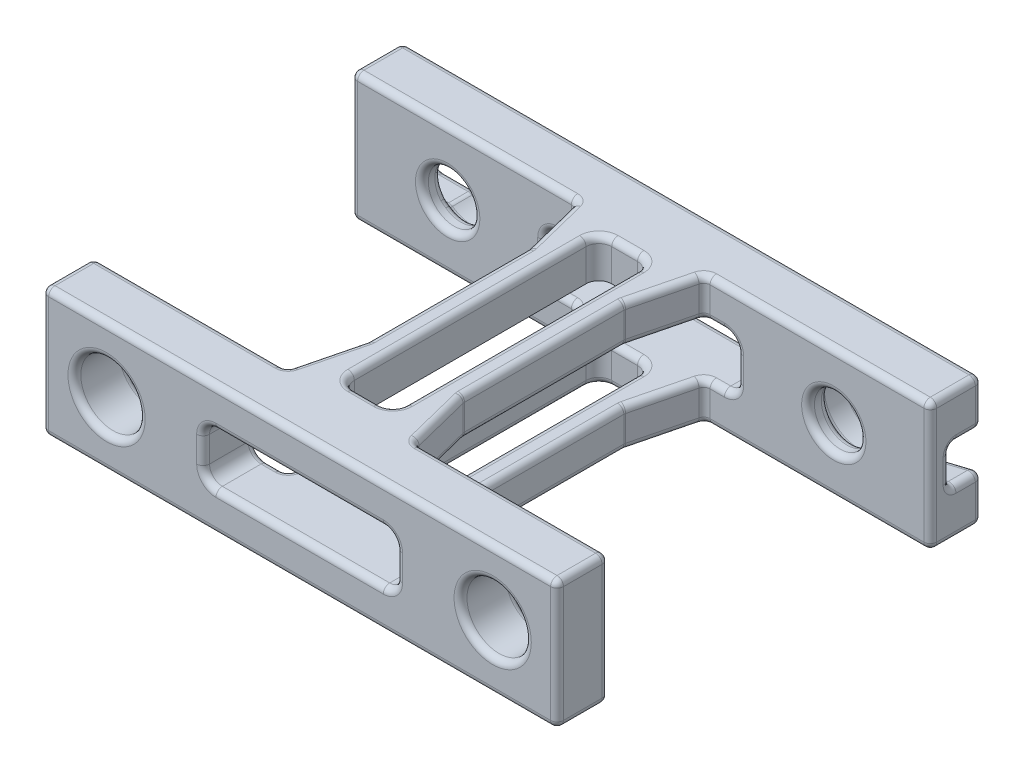
SolidWorks part; units mm, degrees
material "Custom Plastic"
ref_plane "Front Plane" through (0, 0, 0) normal (0, 0, 1) x (1, 0, 0)
ref_plane "Top Plane" through (0, 0, 0) normal (0, 1, 0) x (1, 0, 0)
ref_plane "Right Plane" through (0, 0, 0) normal (1, 0, 0) x (0, 0, -1)
sketch "Sketch1" plane through (0, 0, 0) normal (0, 0, 1) x (1, 0, 0)
  line L1 (-15, 10) -> (15, 10)
  line L2 (-15, 10) -> (-15, -10)
  line L3 (-15, -10) -> (15, -10)
  line L4 (15, 10) -> (15, -10)
  line L5 (-15, 10) -> (15, -10) construction
  line L6 (-15, -10) -> (15, 10) construction
  circle A0 centre (0, 0) radius 2
  dimension "D3" = 4
  dimension "D1" = 20
  dimension "D2" = 30
extrude "Boss-Extrude1" add sketch "Sketch1" along normal blind 8
sketch "Sketch2" plane through (0, 0, 0) normal (0, 0, -1) x (-1, 0, 0)
  line L0 (0, 5.5) -> (0, -5.5) construction
  line L1 (-3.4911, 4.25) -> (-3.4911, -4.25)
  line L2 (-3.4911, 4.25) -> (-8.4911, 4.25)
  line L3 (0, 0) -> (-5.5, 0) construction
  line L4 (-3.4911, -4.25) -> (-8.4911, -4.25)
  line L5 (-18.2077, 1.8863) -> (-8.4911, 4.25)
  line L6 (-18.2077, -1.8863) -> (-8.4911, -4.25)
  circle A1 centre (0, 0) radius 5.5
  arc A2 (0.5609, 0) -> (-17.543, 0) centre (-8.4911, 4.25) ccw
  arc A3 (0.5609, 0) -> (-17.543, 0) centre (-8.4911, -4.25) cw
  arc A4 (-18.2077, 1.8863) -> (-18.2077, -1.8863) centre (-17.543, 0) ccw
  line M3 (-15, 10) -> (-15, -10)
  circle M7 centre (0, 0) radius 2
  dimension "D1" = 11
  dimension "D4" = 20
  dimension "D5" = 4
  dimension "D2" = 8.5
  dimension "D3" = 5
extrude "Cut-Extrude1" cut sketch "Sketch2" against normal blind 5 contours A3 A1 A2 M7 | A3 A2 A1 L1 M7 | L1 A1 | A1 L2 L5 L6 L4 M3
sketch "Sketch3" plane through (0, 10, 0) normal (0, 1, 0) x (1, 0, 0)
  line L0 (-22.5, -53) -> (-22.5, -8)
  line L1 (15, -8) -> (-15, -8)
  line L2 (15, -8) -> (15, 0)
  line L3 (15, 0) -> (-15, 0)
  line L4 (-15, -8) -> (-15, 0)
  line L5 (-15, -8) -> (-30, -8)
  line L6 (-15, -8) -> (-15, 0)
  line L7 (-15, 0) -> (-30, 0)
  line L8 (-30, -8) -> (-30, 0)
  line L9 (-30, -8) -> (-15, -8)
  line L10 (-30, -8) -> (-30, -53)
  line L11 (-30, -53) -> (-15, -53)
  line L12 (-15, -8) -> (-15, -53)
  line L13 (-30, -53) -> (10, -53)
  line L14 (-30, -53) -> (-30, -61)
  line L15 (-30, -61) -> (10, -61)
  line L16 (10, -53) -> (10, -61)
  line L17 (-22.5, -30.5) -> (-15, -30.5) construction
  line L18 (-15, -53) -> (-22.5, -43)
  line L19 (-15, -8) -> (-22.5, -18)
  line L20 (-22.5, -18) -> (-20, -8)
  line L21 (-22.5, -43) -> (-20, -53)
  line M18 (-15, 0) -> (-15, -8)
  dimension "D1" = 15
  dimension "D2" = 45
  dimension "D3" = 8
  dimension "D4" = 40
  dimension "D5" = 10
  dimension "D6" = 5
extrude "Boss-Extrude2" add sketch "Sketch3" against normal blind 20 separate body contours L16 L13 L11 L14 L15 | L12 L5 L10 L11 | L8 L5 L7 M18 | L0 L20 L9 | L21 L0 L11
sketch "Sketch4" plane through (0, 0, 53) normal (0, 0, -1) x (-1, 0, 0)
  circle A0 centre (0, 0) radius 5
  dimension "10" = 10
extrude "Cut-Extrude2" cut sketch "Sketch4" along normal blind 20 and the other way through all
sketch "Sketch5" plane through (0, 0, 5) normal (0, 0, -1) x (-1, 0, 0)
  circle A0 centre (0, 0) radius 2
  circle A1 centre (0, 0) radius 4
  dimension "D1" = 8
extrude "Cut-Extrude3" cut sketch "Sketch5" against normal through all
mirror "Mirror4" about plane through (-30, -10, 0) normal (-1, 0, 0) of bodies 104 105
combine bodies "Combine1" operation type add bodies to combine 106 104 107 105
fillet "Fillet4" radius 1 85 edges at (-37.5, -10, 30.5) (-55, 10, 53) (-70, 10, 57) (-30, 10, 61) (-30, 10, 0) (-38.75, -10, 13) (-57.5, 10, 8) (-38.75, 10, 13) (-37.5, 10, 30.5) (-38.75, 10, 48) (-57.5, -10, 8) (-40, 0, 53) (-70, 0, 53) (-70, 0, 61) (-40, 0, 8) (-37.5, 0, 18) (-37.5, 0, 43) (-30, -10, 0) (-30, -10, 61) (-38.75, -10, 48) (-70, -10, 57) (-55, -10, 53) (-21.25, 10, 48) (-22.5, 0, 43) (-5, 10, 53) (-20, 0, 53) (10, 10, 57) (10, 0, 53) (10, 0, 61) (11.7455, 3.4583, 0) (5.9911, -4.25, 0) (-2.5, 10, 8) (15, 0, 8) (-21.25, -10, 13) (-20, 0, 8) (-22.5, -10, 30.5) (-22.5, 0, 18) (-21.25, -10, 48) (-5, -10, 53) (10, -10, 57) (-2.5, -10, 8) (-22.5, 10, 30.5) (-21.25, 10, 13) (15, 10, 4) (15, -6.3333, 0) (15, 2.6666, 2.5) (15, 6.3333, 0) (15, -10, 4) (5.9911, -4.25, 5) (8.4911, -4.25, 2.5) (11.7455, -3.4583, 0) (15, -2.6666, 2.5) (11.7455, 3.4583, 5) (8.4911, 4.25, 2.5) (5.9911, 4.25, 0) (3.4911, 4.25, 2.5) (-5.5, 0, 0) (3.4911, -4.25, 2.5) (-5.5, 0, 5) (5.9911, 4.25, 5) (15, 0, 5) (11.7455, -3.4583, 5) (4, 0, 8) (-54.5, 0, 0) (-65.9911, 4.25, 0) (-75, 6.3333, 0) (-75, -6.3333, 0) (-71.7455, -3.4583, 0) (-75, 0, 8) (-75, 10, 4) (-75, 0, 5) (-75, -2.6666, 2.5) (-75, -10, 4) (-65.9911, -4.25, 0) (-63.4911, -4.25, 2.5) (-71.7455, -3.4583, 5) (-68.4911, -4.25, 2.5) (-71.7455, 3.4583, 0) (-75, 2.6666, 2.5) (-65.9911, 4.25, 5) (-68.4911, 4.25, 2.5) (-54.5, 0, 5) (-63.4911, 4.25, 2.5) (-65.9911, -4.25, 5) (-71.7455, 3.4583, 5)
fillet "Fillet5" radius 1 9 edges at (-4.5, 0, 5) (-55.5, 0, 5) (-55, 0, 61) (-65, 0, 53) (5, 0, 53) (-5, 0, 61) (-4, 0, 5) (-64, 0, 8) (-56, 0, 5)
sketch "Sketch6" plane through (0, 0, 5) normal (0, 0, -1) x (-1, 0, 0)
  circle A0 centre (0, 0) radius 5
  circle A1 centre (60, 0) radius 5
sketch "Sketch7" plane through (0, -10, 0) normal (0, -1, 0) x (1, 0, 0)
  line L0 (-23.5, 18.1231) -> (-36.5, 42.8769) construction
  line L1 (-23.5, 18.1231) -> (-36.5, 18.1231)
  line L2 (-23.5, 18.1231) -> (-23.5, 42.8769)
  line L3 (-23.5, 42.8769) -> (-36.5, 42.8769)
  line L4 (-36.5, 18.1231) -> (-36.5, 42.8769)
  line L6 (-28, 10.5) -> (-32, 10.5)
  line L7 (-26, 12.5) -> (-26, 48.5)
  line L8 (-28, 50.5) -> (-32, 50.5)
  line L9 (-34, 12.5) -> (-34, 48.5)
  line L10 (-26, 10.5) -> (-34, 50.5) construction
  line L11 (-26, 50.5) -> (-34, 10.5) construction
  arc A0 (-34, 12.5) -> (-32, 10.5) centre (-32, 12.5) ccw
  arc A1 (-32, 50.5) -> (-34, 48.5) centre (-32, 48.5) ccw
  arc A2 (-28, 50.5) -> (-26, 48.5) centre (-28, 48.5) cw
  arc A3 (-26, 12.5) -> (-28, 10.5) centre (-28, 12.5) cw
  point P6 (-30, 30.5)
  dimension "D3" = 2
  dimension "D1" = 40
  dimension "D2" = 8
extrude "Cut-Extrude4" cut sketch "Sketch7" against normal through all contours A3 L7 L1 L9 A0 L6 | L9 L1 L7 L3 | A2 L8 A1 L9 L3 L7
fillet "Fillet6" radius 1 16 edges at (-33.4142, 10, 11.0858) (-30, 10, 10.5) (-26.5858, 10, 11.0858) (-26, 10, 30.5) (-26.5858, 10, 49.9142) (-30, 10, 50.5) (-33.4142, 10, 49.9142) (-33.4142, -10, 11.0858) (-30, -10, 10.5) (-26.5858, -10, 11.0858) (-26, -10, 30.5) (-26.5858, -10, 49.9142) (-30, -10, 50.5) (-33.4142, -10, 49.9142) (-34, 10, 30.5) (-34, -10, 30.5)
sketch "Sketch8" plane through (0, 0, 61) normal (0, 0, 1) x (1, 0, 0)
  line L0 (-69, -9) -> (9, 9) construction
  line L1 (-69, -9) -> (9, -9)
  line L2 (-69, -9) -> (-69, 9)
  line L3 (-69, 9) -> (9, 9)
  line L4 (9, -9) -> (9, 9)
  line L6 (-43, -4) -> (-17, -4)
  line L7 (-45, -2) -> (-45, 2)
  line L8 (-43, 4) -> (-17, 4)
  line L9 (-15, -2) -> (-15, 2)
  line L10 (-45, -4) -> (-15, 4) construction
  line L11 (-45, 4) -> (-15, -4) construction
  arc A0 (-15, 2) -> (-17, 4) centre (-17, 2) ccw
  arc A1 (-15, -2) -> (-17, -4) centre (-17, -2) cw
  arc A2 (-45, 2) -> (-43, 4) centre (-43, 2) cw
  arc A3 (-43, -4) -> (-45, -2) centre (-43, -2) cw
  point P6 (-30, 0)
  dimension "D3" = 2
  dimension "D1" = 30
  dimension "D2" = 8
extrude "Cut-Extrude5" cut sketch "Sketch8" against normal through all and the other way through all contours L7 A2 L8 A0 L9 A1 L6 A3
fillet "Fillet7" radius 1 72 edges at (-38.6702, 4, 13.319) (-37.5075, 4, 18.0009) (-37.5, 4, 30.5) (-37.5075, 4, 42.9991) (-38.6702, 4, 47.681) (-44.4142, -3.4142, 53) (-44.4142, -3.4142, 61) (-44.4142, -3.4142, 8) (-44.4142, -3.4142, 0) (-45, 0, 53) (-45, 0, 61) (-45, 0, 8) (-45, 0, 0) (-44.4142, 3.4142, 53) (-44.4142, 3.4142, 61) (-44.4142, 3.4142, 8) (-44.4142, 3.4142, 0) (-30, 4, 0) (-30, 4, 61) (-15.5858, 3.4142, 61) (-15.5858, 3.4142, 53) (-15.5858, 3.4142, 0) (-15.5858, 3.4142, 8) (-15, 0, 61) (-15, 0, 53) (-15, 0, 0) (-15, 0, 8) (-15.5858, -3.4142, 53) (-15.5858, -3.4142, 61) (-15.5858, -3.4142, 8) (-15.5858, -3.4142, 0) (-21.3298, 4, 13.319) (-22.4925, 4, 18.0009) (-22.5, 4, 30.5) (-22.4925, 4, 42.9991) (-21.3298, 4, 47.681) (-30, -4, 10.5) (-33.4142, -4, 11.0858) (-34, -4, 30.5) (-33.4142, -4, 49.9142) (-30, -4, 50.5) (-26.5858, -4, 49.9142) (-26, -4, 30.5) (-26.5858, -4, 11.0858) (-38.6702, -4, 47.681) (-37.5075, -4, 42.9991) (-37.5, -4, 30.5) (-37.5075, -4, 18.0009) (-38.6702, -4, 13.319) (-30, -4, 61) (-30, -4, 0) (-21.3298, -4, 13.319) (-22.4925, -4, 18.0009) (-22.5, -4, 30.5) (-22.4925, -4, 42.9991) (-21.3298, -4, 47.681) (-41.8904, 4, 53) (-40.1654, 4, 52.7882) (-40.1654, 4, 8.2118) (-41.8904, 4, 8) (-18.1096, 4, 8) (-19.8346, 4, 8.2118) (-19.8346, 4, 52.7882) (-18.1096, 4, 53) (-41.8904, -4, 53) (-40.1654, -4, 52.7882) (-40.1654, -4, 8.2118) (-41.8904, -4, 8) (-18.1096, -4, 8) (-19.8346, -4, 8.2118) (-19.8346, -4, 52.7882) (-18.1096, -4, 53)
